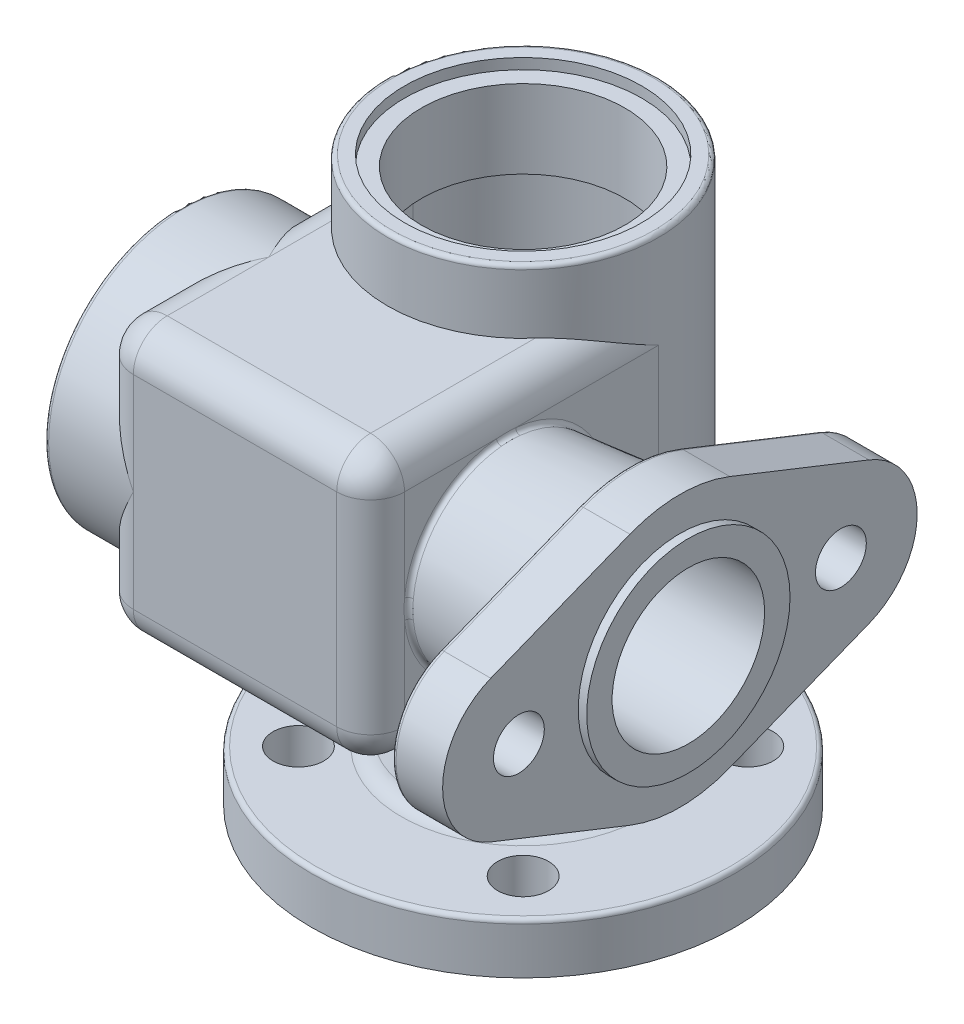
SolidWorks part; units mm, degrees
ref_plane "前基準面" through (0, 0, 0) normal (0, 0, 1) x (1, 0, 0)
ref_plane "上基準面" through (0, 0, 0) normal (0, 1, 0) x (1, 0, 0)
ref_plane "右基準面" through (0, 0, 0) normal (1, 0, 0) x (0, 0, -1)
sketch "草圖1" plane through (0, 0, 0) normal (0, 0, 1) x (1, 0, 0)
  line L0 (0, 0) -> (30, 0)
  line L1 (30, 0) -> (30, 2)
  line L2 (30, 2) -> (50, 2)
  line L3 (50, 2) -> (50, 13)
  line L4 (49, 14) -> (28.772, 14)
  line L5 (25.0267, 16.5955) -> (20.9737, 27.4035)
  line L6 (32, 54.98) -> (32, 134)
  line L7 (31, 135) -> (0, 135)
  line L8 (0, 0) -> (0, 162.4144) construction
  line L9 (0, 0) -> (0, 135)
  arc A0 (21.9724, 31.716) -> (32, 54.98) centre (0, 54.98) ccw
  arc A1 (20.9737, 27.4035) -> (21.9724, 31.716) centre (24.719, 28.808) cw
  arc A2 (32, 134) -> (31, 135) centre (31, 134) ccw
  arc A3 (50, 13) -> (49, 14) centre (49, 13) ccw
  arc A4 (28.772, 14) -> (25.0267, 16.5955) centre (28.772, 18) cw
  point P15 (20, 30)
  point P18 (32, 135)
  point P21 (50, 14)
  point P24 (26, 14)
  dimension "D8" = 32
  dimension "D11" = 4
  dimension "D12" = 1
  dimension "D13" = 4
  dimension "D1" = 32
  dimension "D2" = 30
  dimension "D3" = 2
  dimension "D4" = 50
  dimension "D5" = 20
  dimension "D6" = 28
  dimension "D7" = 26
  dimension "D9" = 133
  dimension "D10" = 12
revolve "旋轉1" add sketch "草圖1" angle 360 about L8
ref_plane "平面1" through (0, 0, 36) normal (0, 0, 1) x (1, 0, 0)
sketch "草圖2" plane through (0, 0, 36) normal (0, 0, 1) x (1, 0, 0)
  line L0 (32, 54.98) -> (32, 134) construction
  line L1 (-32, 56) -> (32, 56)
  line L2 (-32, 56) -> (-32, 120)
  line L3 (-32, 120) -> (32, 120)
  line L4 (32, 56) -> (32, 120)
  line L5 (-32, 134) -> (-32, 54.98) construction
  line L6 (-32, 88) -> (37.439, 88) construction
  line L7 (-50, 2) -> (50, 2) construction
  dimension "D1" = 64
  dimension "D2" = 86
extrude "填料-伸長1" add sketch "草圖2" against normal up to next and the other way blind 32
fillet "圓角1" radius 8 4 edges at (-32, 56, 34) (32, 56, 34) (32, 120, 34) (-32, 120, 34)
fillet "圓角2" radius 8 8 edges at (-29.6569, 117.6569, 68) (0, 120, 68) (29.6569, 117.6569, 68) (32, 88, 68) (29.6569, 58.3431, 68) (0, 56, 68) (-29.6569, 58.3431, 68) (-32, 88, 68)
sketch "草圖3" plane through (32, 0, 0) normal (1, 0, 0) x (0, 0, -1)
  line L0 (0, 112) -> (0, 64) construction
  line L1 (-68, 88) -> (8.6002, 88) construction
  line L2 (-68, 64) -> (-68, 112) construction
  circle A0 centre (-36, 88) radius 23
  dimension "D1" = 46
  dimension "D2" = 36
ref_plane "平面2" through (61, 0, 0) normal (1, 0, 0) x (0, 0, -1)
sketch "草圖4" plane through (61, 0, 0) normal (1, 0, 0) x (0, 0, -1)
  circle A0 centre (-36, 88) radius 26
  dimension "D1" = 52
loft "疊層拉伸1" add profiles "草圖4", "草圖3" connector at (61, 111.3085, 47.5201) connector at (32, 106.5819, 49.5541)
sketch "草圖5" plane through (61, 0, 0) normal (1, 0, 0) x (0, 0, -1)
  line L0 (-36, 88) -> (-74, 88) construction
  line L1 (-80.6316, 104.7339) -> (-47.7895, 117.7491)
  line L2 (-80.6316, 71.2661) -> (-47.7895, 58.2509)
  line L3 (-36, 88) -> (-36, 78.8383) construction
  line L4 (8.6316, 104.7339) -> (-24.2105, 117.7491)
  line L5 (8.6316, 71.2661) -> (-24.2105, 58.2509)
  arc A0 (-47.7895, 58.2509) -> (-24.2105, 58.2509) centre (-36, 88) ccw
  arc A1 (-80.6316, 104.7339) -> (-80.6316, 71.2661) centre (-74, 88) ccw
  arc A2 (8.6316, 104.7339) -> (8.6316, 71.2661) centre (2, 88) cw
  arc A3 (-24.2105, 117.7491) -> (-47.7895, 117.7491) centre (-36, 88) ccw
  dimension "D1" = 64
  dimension "D2" = 36
  dimension "D3" = 38
extrude "填料-伸長2" add sketch "草圖5" along normal blind 12
sketch "草圖6" plane through (73, 0, 0) normal (1, 0, 0) x (0, 0, -1)
  circle A0 centre (-36, 88) radius 24
  dimension "D1" = 48
extrude "填料-伸長3" add sketch "草圖6" along normal blind 2
sketch "草圖7" plane through (73, 0, 0) normal (1, 0, 0) x (0, 0, -1)
  line L0 (-36, 88) -> (-36, 77.9752) construction
  line L1 (-36, 88) -> (12.0831, 88) construction
  line L2 (-36, 88) -> (-83.5033, 88) construction
  circle A0 centre (-74, 88) radius 6
  circle A1 centre (2, 88) radius 6
  dimension "D1" = 12
  dimension "D2" = 76
extrude "除料-伸長1" cut sketch "草圖7" against normal up to next
sketch "草圖8" plane through (75, 0, 0) normal (1, 0, 0) x (0, 0, -1)
  circle A0 centre (-36, 88) radius 18
  dimension "D1" = 36
extrude "除料-伸長2" cut sketch "草圖8" against normal up to surface (43 mm away) up to face at (32, 88, 13)
ref_plane "平面3" through (0, 62, 0) normal (0, 1, 0) x (1, 0, 0)
sketch "草圖9" plane through (0, 62, 0) normal (0, 1, 0) x (1, 0, 0)
  line L1 (26, 0) -> (26, -62)
  line L2 (26, -62) -> (-26, -62)
  line L3 (-26, -62) -> (-26, 0)
  line L4 (-24, -68) -> (24, -68) construction
  arc A0 (26, 0) -> (-26, 0) centre (0, 0) ccw
  dimension "D1" = 52
  dimension "D2" = 6
extrude "除料-伸長3" cut sketch "草圖9" along normal blind 52
sketch "草圖10" plane through (0, 135, 0) normal (0, 1, 0) x (1, 0, 0)
  circle A0 centre (0, 0) radius 28
  dimension "D1" = 56
extrude "除料-伸長4" cut sketch "草圖10" against normal blind 2.5
sketch "草圖11" plane through (0, 132.5, 0) normal (0, 1, 0) x (1, 0, 0)
  circle A0 centre (0, 0) radius 24
  dimension "D1" = 48
extrude "除料-伸長5" cut sketch "草圖11" against normal up to next
sketch "草圖12" plane through (0, 0, 0) normal (0, -1, 0) x (1, 0, 0)
  circle A0 centre (0, 0) radius 12.5
  dimension "D1" = 25
extrude "除料-伸長6" cut sketch "草圖12" against normal blind 39
sketch "草圖13" plane through (0, 39, 0) normal (0, -1, 0) x (1, 0, 0)
  circle A0 centre (0, 0) radius 18
  dimension "D1" = 36
extrude "除料-伸長7" cut sketch "草圖13" against normal blind 10
ref_plane "平面4" through (-45, 0, 0) normal (1, 0, 0) x (0, 0, -1)
sketch "草圖15" plane through (-45, 0, 0) normal (1, 0, 0) x (0, 0, -1)
  line L0 (-74, 88) -> (-12.388, 88) construction
  circle A0 centre (-36, 88) radius 32
  circle A2 centre (-36, 88) radius 24
  circle A3 centre (-36, 88) radius 24 construction
  dimension "D1" = 64
  dimension "D2" = 0
extrude "填料-伸長4" add sketch "草圖15" along normal up to next
sketch "草圖16" plane through (-45, 0, 0) normal (-1, 0, 0) x (0, 0, 1)
  circle A0 centre (36, 88) radius 24
  dimension "D1" = 48
extrude "除料-伸長8" cut sketch "草圖16" against normal blind 4
sketch "草圖17" plane through (-41, 0, 0) normal (-1, 0, 0) x (0, 0, 1)
  circle A0 centre (36, 88) radius 19.5
  dimension "D1" = 39
extrude "除料-伸長9" cut sketch "草圖17" against normal up to next
sketch "草圖18" plane through (0, 14, 0) normal (0, 1, 0) x (1, 0, 0)
  line L0 (0, 0) -> (14.2872, 0) construction
  line L1 (0, 0) -> (44.8716, 44.8716) construction
  circle A0 centre (0, 0) radius 37.5 construction
  circle A1 centre (26.5165, 26.5165) radius 6
  dimension "D1" = 75
  dimension "D3" = 12
  dimension "D2" = 45
extrude "除料-伸長10" cut sketch "草圖18" against normal through all
ref_axis "基準軸1" through (0, -6.75, 0) along (0, 1, 0)
pattern_circular "環狀複製排列1" count 4 over 360 about axis through (0, -6.75, 0) along (0, 1, 0) of "除料-伸長10"
fillet "圓角3" radius 1 8 edges at (61, 120, 36) (61, 111.2415, 7.7895) (61, 88, -20) (61, 64.7585, 7.7895) (61, 56, 36) (61, 64.7585, 64.2105) (61, 88, 92) (61, 111.2415, 64.2105)
fillet "圓角4" radius 1 3 edges at (-45, 88, 4) (32, 88, 13) (61, 88, 10)
sketch "草圖19" plane through (-41, 0, 0) normal (-1, 0, 0) x (0, 0, 1)
  circle A1 centre (36, 88) radius 19.5
  circle A2 centre (36, 88) radius 19.5
  dimension "D1" = 0
ref_plane "平面5" through (0, 86, 0) normal (0, 1, 0) x (1, 0, 0)
